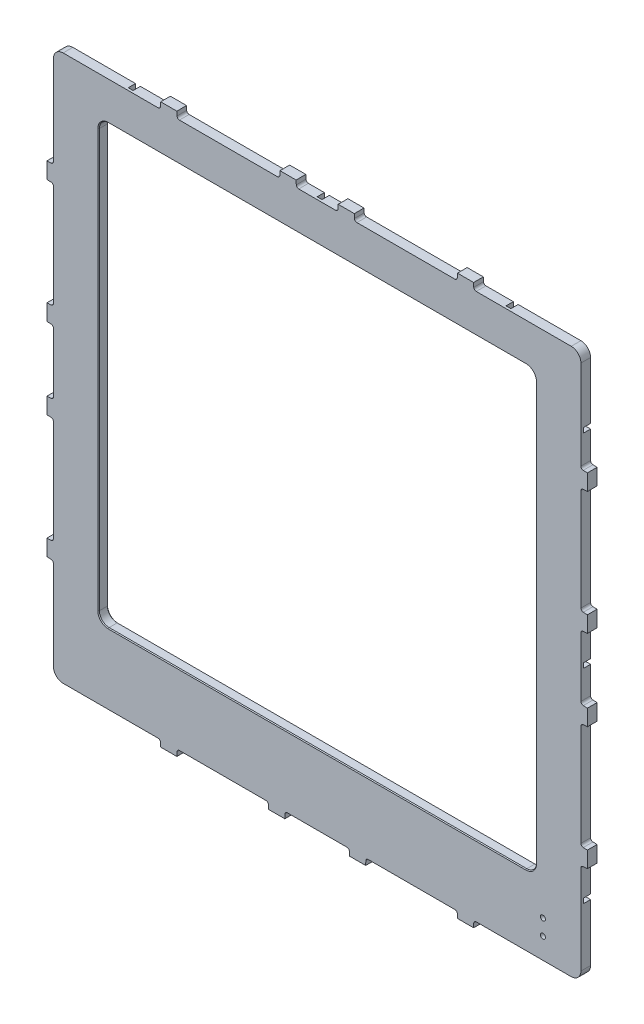
SolidWorks part; units mm, degrees
ref_plane "Alzado" through (0, 0, 0) normal (0, 0, 1) x (1, 0, 0)
ref_plane "Planta" through (0, 0, 0) normal (0, 1, 0) x (1, 0, 0)
ref_plane "Vista lateral" through (0, 0, 0) normal (1, 0, 0) x (0, 0, -1)
ref_plane "Plano1" through (0, 0, -3) normal (0, 0, -1) x (-1, 0, 0)
sketch "Croquis1" plane through (0, 0, -3) normal (0, 0, -1) x (-1, 0, 0)
  line L0 (-167.1, -172.8) -> (167.1, -172.8)
  line L1 (167.1, -172.8) -> (167.1, 172.8)
  line L2 (167.1, 172.8) -> (-167.1, 172.8)
  line L3 (-167.1, 172.8) -> (-167.1, -172.8)
  dimension "D1" = 334.2
  dimension "D2" = 345.6
extrude "Saliente-Extruir1" add sketch "Croquis1" against normal blind 6
sketch "Croquis2" plane through (0, 0, 3) normal (0, 0, 1) x (1, 0, 0)
  line L0 (-167.1, -172.8) -> (-96.8897, -172.8)
  line L1 (-96.8897, -172.8) -> (-96.8897, -168.8)
  line L2 (-96.8897, -168.8) -> (-167.1, -168.8)
  line L3 (-167.1, -168.8) -> (-167.1, -172.8)
  line L4 (167.1, 172.8) -> (167.1, -172.8) construction
  line L5 (-167.1, 172.8) -> (167.1, 172.8) construction
  dimension "D1" = 263.9897
  dimension "D2" = 334.2
  dimension "D3" = 341.6
  dimension "D4" = 345.6
extrude "Cortar-Extruir1" cut sketch "Croquis2" against normal through all
sketch "Croquis3" plane through (0, 0, 3) normal (0, 0, 1) x (1, 0, 0)
  line L0 (-163.1, -168.8) -> (-163.1, -106)
  line L1 (-163.1, -106) -> (-167.1, -106)
  line L2 (-167.1, -106) -> (-167.1, -168.8)
  line L3 (-167.1, -168.8) -> (-163.1, -168.8)
  line L4 (-167.1, -168.8) -> (-167.1, 172.8) construction
  line L5 (-96.8897, -168.8) -> (-167.1, -168.8) construction
  dimension "D1" = 4
  dimension "D2" = 62.8
extrude "Cortar-Extruir2" cut sketch "Croquis3" against normal through all
sketch "Croquis4" plane through (0, 0, 3) normal (0, 0, 1) x (1, 0, 0)
  line L0 (-167.1, 172.8) -> (-167.1, 106.1397)
  line L1 (-167.1, 106.1397) -> (-163.1, 106.1397)
  line L2 (-163.1, 106.1397) -> (-163.1, 172.8)
  line L3 (-163.1, 172.8) -> (-167.1, 172.8)
  line L4 (-167.1, -106) -> (-167.1, 172.8) construction
  line L5 (-96.8897, -168.8) -> (-163.1, -168.8) construction
  dimension "D1" = 4
  dimension "D2" = 274.9397
  dimension "D3" = 341.6
extrude "Cortar-Extruir3" cut sketch "Croquis4" against normal through all
sketch "Croquis5" plane through (0, 0, 3) normal (0, 0, 1) x (1, 0, 0)
  line L0 (-163.1, 168.8) -> (-96.75, 168.8)
  line L1 (-96.75, 168.8) -> (-96.75, 172.8)
  line L2 (-96.75, 172.8) -> (-163.1, 172.8)
  line L3 (-163.1, 172.8) -> (-163.1, 168.8)
  line L4 (-167.1, -106) -> (-167.1, 106.1397) construction
  line L5 (-163.1, -106) -> (-167.1, -106) construction
  dimension "D1" = 4
  dimension "D2" = 70.35
  dimension "D3" = 274.8
  dimension "D4" = 278.8
extrude "Cortar-Extruir4" cut sketch "Croquis5" against normal through all
sketch "Croquis6" plane through (0, 0, 3) normal (0, 0, 1) x (1, 0, 0)
  line L0 (-12.8603, 172.8) -> (-12.8603, 168.8)
  line L1 (-12.8603, 168.8) -> (12.8603, 168.8)
  line L2 (12.8603, 168.8) -> (12.8603, 172.8)
  line L3 (12.8603, 172.8) -> (-12.8603, 172.8)
  line L4 (-167.1, -106) -> (-167.1, 106.1397) construction
  line L5 (-96.75, 172.8) -> (167.1, 172.8) construction
  dimension "D1" = 154.2397
  dimension "D2" = 179.9603
  dimension "D3" = 4
extrude "Cortar-Extruir5" cut sketch "Croquis6" against normal through all
sketch "Croquis7" plane through (0, 0, 3) normal (0, 0, 1) x (1, 0, 0)
  line L0 (167.1, 172.8) -> (96.8897, 172.8)
  line L1 (96.8897, 172.8) -> (96.8897, 168.8)
  line L2 (96.8897, 168.8) -> (167.1, 168.8)
  line L3 (167.1, 168.8) -> (167.1, 172.8)
  line L4 (-163.1, 106.1397) -> (-163.1, 168.8) construction
  line L5 (-96.75, 172.8) -> (-12.8603, 172.8) construction
  dimension "D1" = 259.9897
  dimension "D2" = 330.2
  dimension "D3" = 4
extrude "Cortar-Extruir6" cut sketch "Croquis7" against normal through all
sketch "Croquis8" plane through (0, 0, 3) normal (0, 0, 1) x (1, 0, 0)
  line L0 (163.1, 168.8) -> (163.1, 106)
  line L1 (163.1, 106) -> (167.1, 106)
  line L2 (167.1, 106) -> (167.1, 168.8)
  line L3 (167.1, 168.8) -> (163.1, 168.8)
  line L4 (-96.75, 168.8) -> (-96.75, 172.8) construction
  line L5 (-96.75, 172.8) -> (-12.8603, 172.8) construction
  dimension "D1" = 259.85
  dimension "D2" = 263.85
  dimension "D3" = 4
  dimension "D4" = 66.8
extrude "Cortar-Extruir7" cut sketch "Croquis8" against normal through all
sketch "Croquis9" plane through (0, 0, 3) normal (0, 0, 1) x (1, 0, 0)
  line L0 (167.1, 19.8603) -> (163.1, 19.8603)
  line L1 (163.1, 19.8603) -> (163.1, -19.8603)
  line L2 (163.1, -19.8603) -> (167.1, -19.8603)
  line L3 (167.1, -19.8603) -> (167.1, 19.8603)
  line L4 (167.1, 106) -> (167.1, -172.8) construction
  line L5 (12.8603, 172.8) -> (96.8897, 172.8) construction
  dimension "D1" = 4
  dimension "D2" = 152.9397
  dimension "D3" = 192.6603
extrude "Cortar-Extruir8" cut sketch "Croquis9" against normal through all
sketch "Croquis10" plane through (0, 0, 3) normal (0, 0, 1) x (1, 0, 0)
  line L0 (167.1, -172.8) -> (167.1, -106.1397)
  line L1 (167.1, -106.1397) -> (163.1, -106.1397)
  line L2 (163.1, -106.1397) -> (163.1, -172.8)
  line L3 (163.1, -172.8) -> (167.1, -172.8)
  line L4 (167.1, 106) -> (167.1, 19.8603) construction
  line L5 (12.8603, 172.8) -> (96.8897, 172.8) construction
  dimension "D1" = 4
  dimension "D2" = 278.9397
  dimension "D3" = 345.6
extrude "Cortar-Extruir9" cut sketch "Croquis10" against normal through all
sketch "Croquis11" plane through (0, 0, 3) normal (0, 0, 1) x (1, 0, 0)
  line L0 (163.1, -168.8) -> (96.8897, -168.8)
  line L1 (96.8897, -168.8) -> (96.8897, -172.8)
  line L2 (96.8897, -172.8) -> (163.1, -172.8)
  line L3 (163.1, -172.8) -> (163.1, -168.8)
  line L4 (167.1, -19.8603) -> (167.1, -106.1397) construction
  line L5 (163.1, -172.8) -> (-96.8897, -172.8) construction
  dimension "D1" = 4
  dimension "D2" = 70.2103
  dimension "D3" = 4
extrude "Cortar-Extruir10" cut sketch "Croquis11" against normal through all
sketch "Croquis12" plane through (0, 0, 3) normal (0, 0, 1) x (1, 0, 0)
  line L0 (86.6103, -172.8) -> (86.6103, -168.8)
  line L1 (86.6103, -168.8) -> (30.1397, -168.8)
  line L2 (30.1397, -168.8) -> (30.1397, -172.8)
  line L3 (30.1397, -172.8) -> (86.6103, -172.8)
  line L4 (167.1, -19.8603) -> (167.1, -106.1397) construction
  line L5 (96.8897, -172.8) -> (-96.8897, -172.8) construction
  dimension "D1" = 80.4897
  dimension "D2" = 136.9603
  dimension "D3" = 4
extrude "Cortar-Extruir11" cut sketch "Croquis12" against normal through all
sketch "Croquis13" plane through (0, 0, -3) normal (0, 0, -1) x (-1, 0, 0)
  line L0 (-1.5, 168.8) -> (-1.5, 162.479)
  line L1 (-2.75, 161) -> (-2.75, 159.6)
  line L2 (-1.5, 158.121) -> (1.5, 158.121)
  line L3 (2.75, 159.6) -> (2.75, 161)
  line L4 (1.5, 162.479) -> (1.5, 168.8)
  line L5 (1.5, 168.8) -> (-1.5, 168.8)
  line L6 (167.1, -106) -> (167.1, 106.1397) construction
  line L7 (-30.1397, -172.8) -> (96.8897, -172.8) construction
  arc A0 (-1.5, 162.479) -> (-2.75, 161) centre (-1.25, 161) ccw
  arc A1 (-2.75, 159.6) -> (-1.5, 158.121) centre (-1.25, 159.6) ccw
  arc A2 (1.5, 158.121) -> (2.75, 159.6) centre (1.25, 159.6) ccw
  arc A3 (2.75, 161) -> (1.5, 162.479) centre (1.25, 161) ccw
  dimension "D1" = 1.5
  dimension "D2" = 1.5
  dimension "D3" = 164.35
  dimension "D4" = 165.6
  dimension "D5" = 168.35
  dimension "D6" = 330.921
extrude "Cortar-Extruir12" cut sketch "Croquis13" against normal blind 4.5
sketch "Croquis14" plane through (0, 0, -3) normal (0, 0, -1) x (-1, 0, 0)
  line L0 (-118.3, 168.8) -> (-118.3, 162.479)
  line L1 (-119.55, 161) -> (-119.55, 159.6)
  line L2 (-118.3, 158.121) -> (-115.3, 158.121)
  line L3 (-114.05, 159.6) -> (-114.05, 161)
  line L4 (-115.3, 162.479) -> (-115.3, 168.8)
  line L5 (-115.3, 168.8) -> (-118.3, 168.8)
  line L6 (2.75, 159.6) -> (2.75, 161) construction
  line L7 (-12.8603, 172.8) -> (-96.8897, 172.8) construction
  arc A0 (-118.3, 162.479) -> (-119.55, 161) centre (-118.05, 161) ccw
  arc A1 (-119.55, 159.6) -> (-118.3, 158.121) centre (-118.05, 159.6) ccw
  arc A2 (-115.3, 158.121) -> (-114.05, 159.6) centre (-115.55, 159.6) ccw
  arc A3 (-114.05, 161) -> (-115.3, 162.479) centre (-115.55, 161) ccw
  dimension "D1" = 1.5
  dimension "D2" = 1.5
  dimension "D3" = 116.8
  dimension "D4" = 118.05
  dimension "D5" = 120.8
  dimension "D6" = 4
  dimension "D7" = 13.2
extrude "Cortar-Extruir13" cut sketch "Croquis14" against normal blind 4.5
sketch "Croquis15" plane through (0, 0, -3) normal (0, 0, -1) x (-1, 0, 0)
  line L0 (-163.1, 124.5) -> (-156.779, 124.5)
  line L1 (-155.3, 123.25) -> (-153.9, 123.25)
  line L2 (-152.421, 124.5) -> (-152.421, 127.5)
  line L3 (-153.9, 128.75) -> (-155.3, 128.75)
  line L4 (-156.779, 127.5) -> (-163.1, 127.5)
  line L5 (-163.1, 127.5) -> (-163.1, 124.5)
  line L6 (-167.1, -19.8603) -> (-167.1, -106.1397) construction
  line L7 (-96.8897, -172.8) -> (-86.6103, -172.8) construction
  arc A0 (-156.779, 124.5) -> (-155.3, 123.25) centre (-155.3, 124.75) ccw
  arc A1 (-153.9, 123.25) -> (-152.421, 124.5) centre (-153.9, 124.75) ccw
  arc A2 (-152.421, 127.5) -> (-153.9, 128.75) centre (-153.9, 127.25) ccw
  arc A3 (-155.3, 128.75) -> (-156.779, 127.5) centre (-155.3, 127.25) ccw
  dimension "D1" = 1.5
  dimension "D2" = 1.5
  dimension "D3" = 4
  dimension "D4" = 10.321
  dimension "D5" = 13.2
  dimension "D6" = 14.679
  dimension "D7" = 297.55
  dimension "D8" = 300.05
extrude "Cortar-Extruir14" cut sketch "Croquis15" against normal blind 4.5
sketch "Croquis16" plane through (0, 0, -3) normal (0, 0, -1) x (-1, 0, 0)
  line L0 (-163.1, -1.5) -> (-156.779, -1.5)
  line L1 (-155.3, -2.75) -> (-153.9, -2.75)
  line L2 (-152.421, -1.5) -> (-152.421, 1.5)
  line L3 (-153.9, 2.75) -> (-155.3, 2.75)
  line L4 (-156.779, 1.5) -> (-163.1, 1.5)
  line L5 (-163.1, 1.5) -> (-163.1, -1.5)
  line L6 (167.1, -106) -> (167.1, 106.1397) construction
  line L7 (-30.1397, -172.8) -> (96.8897, -172.8) construction
  arc A0 (-156.779, -1.5) -> (-155.3, -2.75) centre (-155.3, -1.25) ccw
  arc A1 (-153.9, -2.75) -> (-152.421, -1.5) centre (-153.9, -1.25) ccw
  arc A2 (-152.421, 1.5) -> (-153.9, 2.75) centre (-153.9, 1.25) ccw
  arc A3 (-155.3, 2.75) -> (-156.779, 1.5) centre (-155.3, 1.25) ccw
  dimension "D1" = 1.5
  dimension "D2" = 1.5
  dimension "D3" = 170.05
  dimension "D7" = 330.2
extrude "Cortar-Extruir15" cut sketch "Croquis16" against normal blind 4.5
sketch "Croquis17" plane through (0, 0, -3) normal (0, 0, -1) x (-1, 0, 0)
  line L0 (-163.1, -127.5) -> (-156.779, -127.5)
  line L1 (-155.3, -128.75) -> (-153.9, -128.75)
  line L2 (-152.421, -127.5) -> (-152.421, -124.5)
  line L3 (-153.9, -123.25) -> (-155.3, -123.25)
  line L4 (-156.779, -124.5) -> (-163.1, -124.5)
  line L5 (-163.1, -124.5) -> (-163.1, -127.5)
  line L6 (167.1, -106) -> (167.1, 106.1397) construction
  line L7 (-30.1397, -172.8) -> (96.8897, -172.8) construction
  arc A0 (-156.779, -127.5) -> (-155.3, -128.75) centre (-155.3, -127.25) ccw
  arc A1 (-153.9, -128.75) -> (-152.421, -127.5) centre (-153.9, -127.25) ccw
  arc A2 (-152.421, -124.5) -> (-153.9, -123.25) centre (-153.9, -124.75) ccw
  arc A3 (-155.3, -123.25) -> (-156.779, -124.5) centre (-155.3, -124.75) ccw
  dimension "D1" = 1.5
  dimension "D2" = 1.5
  dimension "D3" = 44.05
  dimension "D7" = 330.2
extrude "Cortar-Extruir16" cut sketch "Croquis17" against normal blind 4.5
sketch "Croquis18" plane through (0, 0, -3) normal (0, 0, -1) x (-1, 0, 0)
  line L0 (-115.3, -168.8) -> (-115.3, -162.479)
  line L1 (-114.05, -161) -> (-114.05, -159.6)
  line L2 (-115.3, -158.121) -> (-118.3, -158.121)
  line L3 (-119.55, -159.6) -> (-119.55, -161)
  line L4 (-118.3, -162.479) -> (-118.3, -168.8)
  line L5 (-118.3, -168.8) -> (-115.3, -168.8)
  line L6 (167.1, -106) -> (167.1, 106.1397) construction
  line L7 (-30.1397, -172.8) -> (96.8897, -172.8) construction
  arc A0 (-115.3, -162.479) -> (-114.05, -161) centre (-115.55, -161) ccw
  arc A1 (-114.05, -159.6) -> (-115.3, -158.121) centre (-115.55, -159.6) ccw
  arc A2 (-118.3, -158.121) -> (-119.55, -159.6) centre (-118.05, -159.6) ccw
  arc A3 (-119.55, -161) -> (-118.3, -162.479) centre (-118.05, -161) ccw
  dimension "D1" = 1.5
  dimension "D2" = 1.5
  dimension "D3" = 282.65
  dimension "D4" = 285.15
  dimension "D5" = 13.2
extrude "Cortar-Extruir17" cut sketch "Croquis18" against normal blind 4.5
sketch "Croquis19" plane through (0, 0, -3) normal (0, 0, -1) x (-1, 0, 0)
  line L0 (-56.9, -168.8) -> (-56.9, -162.479)
  line L1 (-55.65, -161) -> (-55.65, -159.6)
  line L2 (-56.9, -158.121) -> (-59.9, -158.121)
  line L3 (-61.15, -159.6) -> (-61.15, -161)
  line L4 (-59.9, -162.479) -> (-59.9, -168.8)
  line L5 (-59.9, -168.8) -> (-56.9, -168.8)
  line L6 (167.1, -106) -> (167.1, 106.1397) construction
  line L7 (-30.1397, -172.8) -> (96.8897, -172.8) construction
  arc A0 (-56.9, -162.479) -> (-55.65, -161) centre (-57.15, -161) ccw
  arc A1 (-55.65, -159.6) -> (-56.9, -158.121) centre (-57.15, -159.6) ccw
  arc A2 (-59.9, -158.121) -> (-61.15, -159.6) centre (-59.65, -159.6) ccw
  arc A3 (-61.15, -161) -> (-59.9, -162.479) centre (-59.65, -161) ccw
  dimension "D1" = 1.5
  dimension "D2" = 1.5
  dimension "D3" = 224.25
  dimension "D4" = 226.75
  dimension "D5" = 13.2
  dimension "D6" = 14.679
extrude "Cortar-Extruir18" cut sketch "Croquis19" against normal blind 4.5
sketch "Croquis20" plane through (0, 0, -3) normal (0, 0, -1) x (-1, 0, 0)
  line L0 (-59.7375, -158.121) -> (-57.0625, -158.121)
  line L1 (167.1, -106) -> (167.1, 106.1397) construction
  line L2 (-30.1397, -172.8) -> (96.8897, -172.8) construction
  arc A0 (-57.0625, -158.121) -> (-59.7375, -158.121) centre (-58.4, -158.8) ccw
  dimension "D1" = 1.5
  dimension "D2" = 224.1625
  dimension "D3" = 225.5
  dimension "D4" = 14
extrude "Cortar-Extruir19" cut sketch "Croquis20" against normal blind 4.5
sketch "Croquis21" plane through (0, 0, -3) normal (0, 0, -1) x (-1, 0, 0)
  line L0 (-118.1375, -158.121) -> (-115.4625, -158.121)
  line L1 (167.1, -106) -> (167.1, 106.1397) construction
  line L2 (-30.1397, -172.8) -> (96.8897, -172.8) construction
  arc A0 (-115.4625, -158.121) -> (-118.1375, -158.121) centre (-116.8, -158.8) ccw
  dimension "D1" = 1.5
  dimension "D2" = 282.5625
  dimension "D3" = 283.9
  dimension "D4" = 14
extrude "Cortar-Extruir20" cut sketch "Croquis21" against normal blind 4.5
sketch "Croquis22" plane through (0, 0, -3) normal (0, 0, -1) x (-1, 0, 0)
  line L0 (-152.421, -124.6625) -> (-152.421, -127.3375)
  line L1 (167.1, -106) -> (167.1, 106.1397) construction
  line L2 (-30.1397, -172.8) -> (96.8897, -172.8) construction
  arc A0 (-152.421, -127.3375) -> (-152.421, -124.6625) centre (-153.1, -126) ccw
  dimension "D1" = 1.5
  dimension "D2" = 319.521
  dimension "D3" = 320.2
  dimension "D4" = 45.4625
extrude "Cortar-Extruir21" cut sketch "Croquis22" against normal blind 4.5
sketch "Croquis23" plane through (0, 0, -3) normal (0, 0, -1) x (-1, 0, 0)
  line L0 (-152.421, 1.3375) -> (-152.421, -1.3375)
  line L1 (167.1, -106) -> (167.1, 106.1397) construction
  line L2 (-30.1397, -172.8) -> (96.8897, -172.8) construction
  arc A0 (-152.421, -1.3375) -> (-152.421, 1.3375) centre (-153.1, 0) ccw
  dimension "D1" = 1.5
  dimension "D2" = 319.521
  dimension "D3" = 320.2
  dimension "D4" = 171.4625
extrude "Cortar-Extruir22" cut sketch "Croquis23" against normal blind 4.5
sketch "Croquis24" plane through (0, 0, -3) normal (0, 0, -1) x (-1, 0, 0)
  line L0 (-152.421, 127.3375) -> (-152.421, 124.6625)
  line L1 (96.8897, -172.8) -> (96.8897, -168.8) construction
  line L2 (-30.1397, -172.8) -> (96.8897, -172.8) construction
  arc A0 (-152.421, 124.6625) -> (-152.421, 127.3375) centre (-153.1, 126) ccw
  dimension "D1" = 1.5
  dimension "D2" = 249.3107
  dimension "D3" = 249.9897
  dimension "D4" = 297.4625
extrude "Cortar-Extruir23" cut sketch "Croquis24" against normal blind 4.5
sketch "Croquis25" plane through (0, 0, -3) normal (0, 0, -1) x (-1, 0, 0)
  line L0 (-115.4625, 158.121) -> (-118.1375, 158.121)
  line L1 (-167.1, -19.8603) -> (-167.1, -106.1397) construction
  line L2 (-96.8897, -172.8) -> (-86.6103, -172.8) construction
  arc A0 (-118.1375, 158.121) -> (-115.4625, 158.121) centre (-116.8, 158.8) ccw
  dimension "D1" = 1.5
  dimension "D2" = 48.9625
  dimension "D3" = 50.3
  dimension "D4" = 330.921
extrude "Cortar-Extruir24" cut sketch "Croquis25" against normal blind 4.5
mirror "Simetría1" about plane through (0, 0, 0) normal (1, 0, 0) of "Cortar-Extruir15", "Cortar-Extruir8", "Cortar-Extruir11", "Cortar-Extruir13", "Cortar-Extruir14", "Cortar-Extruir16", "Cortar-Extruir17", "Cortar-Extruir18", "Cortar-Extruir19", "Cortar-Extruir20", "Cortar-Extruir21", "Cortar-Extruir22", "Cortar-Extruir23", "Cortar-Extruir24"
sketch "Croquis27" plane through (0, 0, -3) normal (0, 0, -1) x (-1, 0, 0)
  line L0 (1.3375, 158.121) -> (-1.3375, 158.121)
  line L1 (-167.1, 106) -> (-167.1, 19.8603) construction
  line L2 (-12.8603, 172.8) -> (-96.8897, 172.8) construction
  arc A0 (-1.3375, 158.121) -> (1.3375, 158.121) centre (0, 158.8) ccw
  dimension "D1" = 1.5
  dimension "D2" = 165.7625
  dimension "D3" = 167.1
  dimension "D4" = 14
extrude "Cortar-Extruir25" cut sketch "Croquis27" against normal blind 4.5
sketch "Croquis28" plane through (0, 0, 3) normal (0, 0, 1) x (1, 0, 0)
  line L0 (-167.1, -30) -> (-167.1, -96)
  line L1 (-167.1, -96) -> (-163.1, -96)
  line L2 (-163.1, -96) -> (-163.1, -30.1397)
  line L3 (-163.1, -30.1397) -> (-167.1, -30)
  line L4 (-86.6103, -172.8) -> (-86.6103, -168.8) construction
  line L5 (30.1397, -172.8) -> (-30.1397, -172.8) construction
  dimension "D1" = 76.4897
  dimension "D2" = 80.4897
  dimension "D3" = 76.8
  dimension "D4" = 142.6603
  dimension "D5" = 142.8
extrude "Cortar-Extruir26" cut sketch "Croquis28" against normal through all
sketch "Croquis29" plane through (0, 0, 3) normal (0, 0, 1) x (1, 0, 0)
  line L0 (-167.1, 95.8603) -> (-167.1, 30.1397)
  line L1 (-167.1, 30.1397) -> (-163.1, 30.1397)
  line L2 (-163.1, 30.1397) -> (-163.1, 95.8603)
  line L3 (-163.1, 95.8603) -> (-167.1, 95.8603)
  line L4 (-167.1, -106) -> (-167.1, -96) construction
  line L5 (-86.6103, -172.8) -> (-96.8897, -172.8) construction
  dimension "D1" = 4
  dimension "D2" = 202.9397
  dimension "D3" = 268.6603
extrude "Cortar-Extruir27" cut sketch "Croquis29" against normal through all
sketch "Croquis30" plane through (0, 0, 3) normal (0, 0, 1) x (1, 0, 0)
  line L0 (-23, 172.8) -> (-86.75, 172.8)
  line L1 (-86.75, 172.8) -> (-86.75, 168.8)
  line L2 (-86.75, 168.8) -> (-23.1397, 168.8)
  line L3 (-23.1397, 168.8) -> (-23, 172.8)
  line L4 (-167.1, -106) -> (-167.1, -96) construction
  line L5 (-86.6103, -172.8) -> (-96.8897, -172.8) construction
  dimension "D1" = 80.35
  dimension "D2" = 143.9603
  dimension "D3" = 144.1
  dimension "D4" = 341.6
  dimension "D5" = 345.6
extrude "Cortar-Extruir28" cut sketch "Croquis30" against normal through all
sketch "Croquis31" plane through (0, 0, 3) normal (0, 0, 1) x (1, 0, 0)
  line L0 (23.1397, 172.8) -> (23.1397, 168.8)
  line L1 (23.1397, 168.8) -> (86.6103, 168.8)
  line L2 (86.6103, 168.8) -> (86.6103, 172.8)
  line L3 (86.6103, 172.8) -> (23.1397, 172.8)
  line L4 (-167.1, 95.8603) -> (-167.1, 106.1397) construction
  line L5 (-96.75, 172.8) -> (-86.75, 172.8) construction
  dimension "D1" = 190.2397
  dimension "D2" = 253.7103
  dimension "D3" = 4
extrude "Cortar-Extruir29" cut sketch "Croquis31" against normal through all
sketch "Croquis32" plane through (0, 0, 3) normal (0, 0, 1) x (1, 0, 0)
  line L0 (167.1, 96) -> (163.1, 96)
  line L1 (163.1, 96) -> (163.1, 30.1397)
  line L2 (163.1, 30.1397) -> (167.1, 30)
  line L3 (167.1, 30) -> (167.1, 96)
  line L4 (-167.1, 95.8603) -> (-167.1, 106.1397) construction
  line L5 (-96.75, 172.8) -> (-86.75, 172.8) construction
  dimension "D1" = 330.2
  dimension "D2" = 334.2
  dimension "D3" = 76.8
  dimension "D4" = 142.6603
  dimension "D5" = 142.8
extrude "Cortar-Extruir30" cut sketch "Croquis32" against normal through all
sketch "Croquis33" plane through (0, 0, 3) normal (0, 0, 1) x (1, 0, 0)
  line L0 (167.1, -30.1397) -> (163.1, -30.1397)
  line L1 (163.1, -30.1397) -> (163.1, -95.8603)
  line L2 (163.1, -95.8603) -> (167.1, -95.8603)
  line L3 (167.1, -95.8603) -> (167.1, -30.1397)
  line L4 (-167.1, 95.8603) -> (-167.1, 106.1397) construction
  line L5 (-96.75, 172.8) -> (-86.75, 172.8) construction
  dimension "D1" = 330.2
  dimension "D2" = 334.2
  dimension "D3" = 202.9397
  dimension "D4" = 268.6603
extrude "Cortar-Extruir31" cut sketch "Croquis33" against normal through all
sketch "Croquis34" plane through (0, 0, 3) normal (0, 0, 1) x (1, 0, 0)
  line L0 (-19.8603, -172.8) -> (19.8603, -172.8)
  line L1 (19.8603, -172.8) -> (19.8603, -168.8)
  line L2 (19.8603, -168.8) -> (-19.8603, -168.8)
  line L3 (-19.8603, -168.8) -> (-19.8603, -172.8)
  line L4 (167.1, 106) -> (167.1, 96) construction
  line L5 (86.6103, 172.8) -> (96.8897, 172.8) construction
  dimension "D1" = 147.2397
  dimension "D2" = 186.9603
  dimension "D3" = 341.6
  dimension "D4" = 345.6
extrude "Cortar-Extruir32" cut sketch "Croquis34" against normal through all
sketch "Croquis35" plane through (0, 0, 3) normal (0, 0, 1) x (1, 0, 0)
  line L0 (-135.15, 145.06) -> (-135.15, -125.1917)
  line L1 (-135.15, -125.1917) -> (135.15, -125.1917)
  line L2 (135.15, -125.1917) -> (135.15, 145.06)
  line L3 (135.15, 145.06) -> (-135.15, 145.06)
  line L4 (167.1, -95.8603) -> (167.1, -106.1397) construction
  line L5 (96.8897, -172.8) -> (86.6103, -172.8) construction
  dimension "D1" = 31.95
  dimension "D2" = 302.25
  dimension "D3" = 47.6083
  dimension "D4" = 317.86
extrude "Cortar-Extruir33" cut sketch "Croquis35" against normal through all
draft "Ángulo de salida1" type of draft neutral plane draft angle 2 faces to draft 1 face at (96.8897, -170.8, 0) neutral plane through (163.1, -168.8, -3) neutral plane normal (0, -1, 0) parameters "D1"=2
draft "Ángulo de salida2" type of draft neutral plane draft angle 2 faces to draft 1 face at (165.1, -106.1397, 0) neutral plane through (163.1, -106.1397, -3) neutral plane normal (1, 0, 0) parameters "D1"=2
draft "Ángulo de salida3" type of draft neutral plane draft angle 2 faces to draft 1 face at (96.8897, 170.8, 0) neutral plane through (96.8897, 168.8, -3) neutral plane normal (0, 1, 0) parameters "D1"=2
draft "Ángulo de salida4" type of draft neutral plane draft angle 2 faces to draft 1 face at (-165.1, 106.1397, 0) neutral plane through (-163.1, 106.1397, -3) neutral plane normal (-1, 0, 0) parameters "D1"=2
draft "Ángulo de salida5" type of draft neutral plane draft angle 2 faces to draft 1 face at (-96.8897, -170.8, 0) neutral plane through (-96.8897, -168.8, -3) neutral plane normal (0, -1, 0) parameters "D1"=2
draft "Ángulo de salida6" type of draft neutral plane draft angle 2 faces to draft 2 face at (19.8603, -170.8, 0) face at (-19.8603, -170.8, 0) neutral plane through (19.8603, -168.8, -3) neutral plane normal (0, -1, 0) parameters "D1"=2
draft "Ángulo de salida7" type of draft neutral plane draft angle 2 faces to draft 2 face at (165.1, -30.1397, 0) face at (165.1, -95.8603, 0) neutral plane through (163.1, -30.1397, -3) neutral plane normal (1, 0, 0) parameters "D1"=2
draft "Ángulo de salida8" type of draft neutral plane draft angle 2 faces to draft 2 face at (165.1, 96, 0) face at (165.1, 106, 0) neutral plane through (167.1, 172.8, 3) neutral plane normal (1, 0, 0) parameters "D1"=2
draft "Ángulo de salida9" type of draft neutral plane draft angle 2 faces to draft 2 face at (23.1397, 170.8, 0) face at (86.6103, 170.8, 0) neutral plane through (23.1397, 168.8, -3) neutral plane normal (0, 1, 0) parameters "D1"=2
draft "Ángulo de salida10" type of draft neutral plane draft angle 2 faces to draft 2 face at (-96.75, 170.8, 0) face at (-86.75, 170.8, 0) neutral plane through (-167.1, 172.8, 3) neutral plane normal (0, 1, 0) parameters "D1"=2
draft "Ángulo de salida11" type of draft neutral plane draft angle 2 faces to draft 2 face at (-165.1, 30.1397, 0) face at (-165.1, 95.8603, 0) neutral plane through (-163.1, 30.1397, -3) neutral plane normal (-1, 0, 0) parameters "D1"=2
draft "Ángulo de salida12" type of draft neutral plane draft angle 2 faces to draft 2 face at (-165.1, -106, 0) face at (-165.1, -96, 0) neutral plane through (-167.1, -172.8, 3) neutral plane normal (-1, 0, 0) parameters "D1"=2
draft "Ángulo de salida13" type of draft neutral plane draft angle 2 faces to draft 2 face at (30.1397, -170.8, 0) face at (86.6103, -170.8, 0) neutral plane through (86.6103, -168.8, -3) neutral plane normal (0, -1, 0) parameters "D1"=2
draft "Ángulo de salida14" type of draft neutral plane draft angle 2 faces to draft 2 face at (165.1, -19.8603, 0) face at (165.1, 19.8603, 0) neutral plane through (163.1, 19.8603, -3) neutral plane normal (1, 0, 0) parameters "D1"=2
draft "Ángulo de salida15" type of draft neutral plane draft angle 2 faces to draft 2 face at (12.8603, 170.8, 0) face at (-12.8603, 170.8, 0) neutral plane through (-12.8603, 168.8, -3) neutral plane normal (0, 1, 0) parameters "D1"=2
draft "Ángulo de salida16" type of draft neutral plane draft angle 2 faces to draft 2 face at (-165.1, 19.8603, 0) face at (-165.1, -19.8603, 0) neutral plane through (-163.1, 19.8603, -3) neutral plane normal (-1, 0, 0) parameters "D1"=2
draft "Ángulo de salida17" type of draft neutral plane draft angle 2 faces to draft 2 face at (-86.6103, -170.8, 0) face at (-30.1397, -170.8, 0) neutral plane through (-86.6103, -168.8, -3) neutral plane normal (0, -1, 0) parameters "D1"=2
hole_wizard "Diámetro de taladro Ø3.1 (3.1)1" positions "Croquis37" profile "Croquis36" hole size "Ø3.1" standard "Ansi Metric"
sketch "Croquis37" plane through (0, 0, 3) normal (0, 0, 1) x (1, 0, 0)
  point P0 (139.6, -155.8)
  point P1 (139.6, -146.1)
sketch "Croquis36" plane through (139.6, -155.8, 3) normal (1, 0, 0) x (0, -1, 0)
  line L0 (0, 0) -> (0, 6)
  line L1 (0, 6) -> (1.55, 6)
  line L2 (1.55, 6) -> (1.55, 0)
  line L5 (1.55, 0) -> (0, 0)
  line L11 (0, -6.35) -> (0, 107.95) construction
  dimension "Diámetro de taladro hasta el siguiente" = 3.1
  dimension "Profundidad de taladro hasta el siguiente" = 6
hole_wizard "Diámetro de taladro Ø12.0 (12)1" positions "Croquis39" profile "Croquis38" hole size "Ø12.0" standard "Ansi Metric"
sketch "Croquis39" plane through (0, 0, -3) normal (0, 0, -1) x (-1, 0, 0)
  point P0 (80, -148)
  point P1 (-80, -148)
sketch "Croquis38" plane through (-80, -148, -3) normal (1, 0, 0) x (0, 1, 0)
  line L0 (0, 0) -> (0, 4.5)
  line L1 (0, 4.5) -> (6, 4.5)
  line L2 (6, 4.5) -> (6, 0)
  line L5 (6, 0) -> (0, 0)
  line L10 (0, 4.5) -> (-6, 4.5) construction
  line L11 (0, -6.35) -> (0, 107.95) construction
  dimension "Diámetro de taladro" = 12
  dimension "Profundidad de taladro" = 4.5
  dimension "Ángulo de perforador" = 180
fillet "Redondeo1" radius 6 8 edges at (-163.1, 168.8, 0) (163.1, -168.8, 0) (-163.1, -168.8, 0) (163.1, 168.8, 0) (-135.15, 145.06, 0) (135.15, 145.06, 0) (-135.15, -125.1917, 0) (135.15, -125.1917, 0) tangent propagation no
chamfer "Chaflán1" distance 0.5 angle 45 16 edges at (-133.3926, -123.4344, 3) (0, -125.1917, 3) (-135.15, 9.9341, 3) (133.3926, -123.4344, 3) (-133.3926, 143.3026, 3) (135.15, 9.9341, 3) (0, 145.06, 3) (133.3926, 143.3026, 3) (-133.3926, -123.4344, -3) (0, -125.1917, -3) (-135.15, 9.9341, -3) (133.3926, -123.4344, -3) (-133.3926, 143.3026, -3) (135.15, 9.9341, -3) (0, 145.06, -3) (133.3926, 143.3026, -3)
fillet "Redondeo2" radius 1.5 32 edges at (-86.6103, 168.8, 0) (-163.1, -30.1397, 0) (-96.8897, -168.8, 0) (-163.1, 95.8603, 0) (23.1397, 168.8, 0) (19.8603, -168.8, 0) (-30.1397, -168.8, 0) (-163.1, -106.1397, 0) (-163.1, 19.8603, 0) (-12.8603, 168.8, 0) (86.6103, -168.8, 0) (-19.8603, -168.8, 0) (-86.6103, -168.8, 0) (-163.1, -95.8603, 0) (-163.1, -19.8603, 0) (-163.1, 30.1397, 0) (-163.1, 106.1397, 0) (-96.8897, 168.8, 0) (96.8897, 168.8, 0) (-23.1397, 168.8, 0) (163.1, 106.1397, 0) (12.8603, 168.8, 0) (163.1, 30.1397, 0) (86.6103, 168.8, 0) (163.1, -19.8603, 0) (163.1, -95.8603, 0) (163.1, 95.8603, 0) (163.1, 19.8603, 0) (163.1, -30.1397, 0) (163.1, -106.1397, 0) (96.8897, -168.8, 0) (30.1397, -168.8, 0) tangent propagation no
